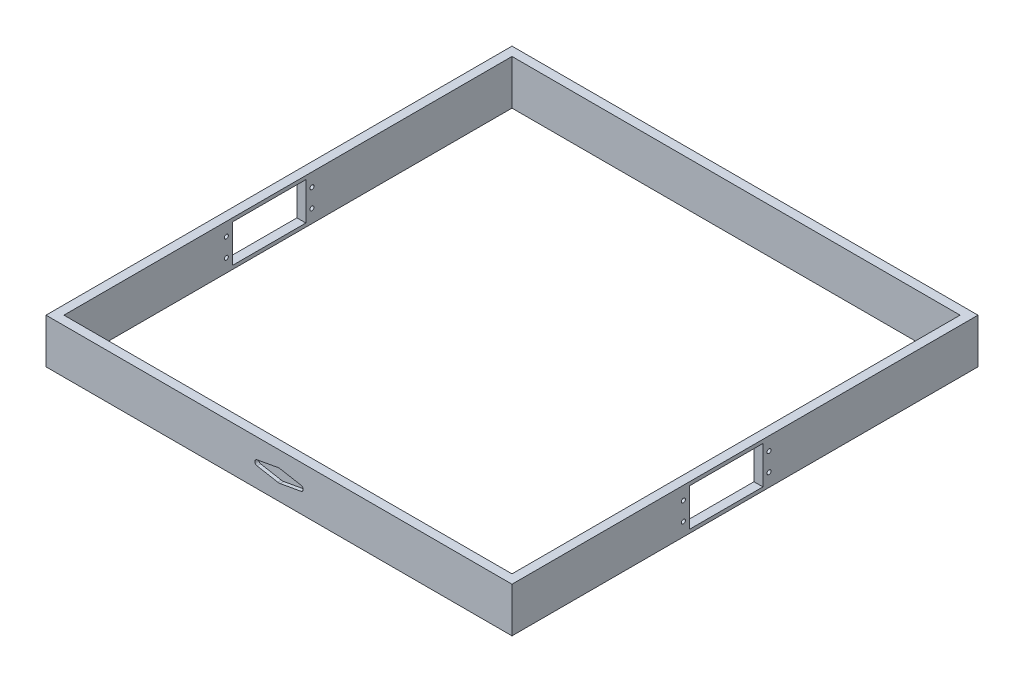
SolidWorks part; units mm, degrees
ref_plane "Front Plane" through (0, 0, 0) normal (0, 0, 1) x (1, 0, 0)
ref_plane "Top Plane" through (0, 0, 0) normal (0, 1, 0) x (1, 0, 0)
ref_plane "Right Plane" through (0, 0, 0) normal (1, 0, 0) x (0, 0, -1)
sketch "Sketch1" plane through (0, 0, 0) normal (0, 1, 0) x (1, 0, 0)
  line L1 (-130.1, -130.1) -> (130.1, -130.1)
  line L2 (-130.1, -130.1) -> (-130.1, 130.1)
  line L3 (-130.1, 130.1) -> (130.1, 130.1)
  line L4 (130.1, -130.1) -> (130.1, 130.1)
  line L5 (-130.1, -130.1) -> (130.1, 130.1) construction
  line L6 (-130.1, 130.1) -> (130.1, -130.1) construction
  point P0 (0, 0)
  dimension "D1" = 260.2
extrude "Boss-Extrude1" add sketch "Sketch1" along normal blind 25
sketch "Sketch2" plane through (0, 25, 0) normal (0, 1, 0) x (1, 0, 0)
  line L0 (130.1, 130.1) -> (-130.1, 130.1) construction
  line L1 (-125.1, -125.1) -> (125.1, -125.1)
  line L2 (-125.1, -125.1) -> (-125.1, 125.1)
  line L3 (-125.1, 125.1) -> (125.1, 125.1)
  line L4 (125.1, -125.1) -> (125.1, 125.1)
  line L5 (-125.1, -125.1) -> (125.1, 125.1) construction
  line L6 (-125.1, 125.1) -> (125.1, -125.1) construction
  point P0 (0, 0)
  dimension "D1" = 5
extrude "Cut-Extrude1" cut sketch "Sketch2" against normal blind 25
sketch "Sketch19" plane through (-130.1, 0, 0) normal (-1, 0, 0) x (0, 0, 1)
  line L0 (-130.1, 25) -> (-130.1, 0) construction
  line L1 (-10, 23) -> (31, 23)
  line L2 (-10, 23) -> (-10, 2)
  line L3 (-10, 2) -> (31, 2)
  line L4 (31, 23) -> (31, 2)
  line L5 (-10, 23) -> (31, 2) construction
  line L6 (-10, 2) -> (31, 23) construction
  line L7 (-130.1, 25) -> (130.1, 25) construction
  point P0 (10.5, 12.5)
  point P7 (-130.1, 12.5)
  point P10 (0, 25)
  dimension "D1" = 41
  dimension "D2" = 21
  dimension "D3" = 10
extrude "Cut-Extrude10" cut sketch "Sketch19" against normal through all
ref_plane "Plane5" through (0, 0, 10.5) normal (0, 0, 1) x (1, 0, 0)
ref_plane "Plane6" through (0, 12.5, 0) normal (0, 1, 0) x (1, 0, 0)
sketch "Sketch21" plane through (-130.1, 0, 0) normal (-1, 0, 0) x (0, 0, 1)
  line L2 (31, 23) -> (-10, 23) construction
  line L3 (-10, 23) -> (-10, 2) construction
  circle A0 centre (-13.4, 17.6) radius 1.125
  point P4 (-10, 12.5)
  point P9 (10.5, 23)
  dimension "D3" = 2.25
  dimension "D1" = 23.9
  dimension "D2" = 5.1
extrude "Cut-Extrude12" cut sketch "Sketch21" against normal through all
mirror "Mirror1" about plane through (0, 0, 10.5) normal (0, 0, 1) of "Cut-Extrude12" second plane through (0, 12.5, 0) second plane normal (0, 1, 0)
ref_plane "Plane7" through (0, 0, 0) normal (-1, 0, 0) x (0, 0, 1)
sketch "Sketch22" plane through (0, 0, 130.1) normal (0, 0, 1) x (1, 0, 0)
  line L0 (-130.1, 25) -> (-130.1, 0) construction
  line L1 (-12.2663, 13.9762) -> (-0.6443, 16.0724)
  line L2 (-12.2663, 11.0238) -> (-0.6443, 8.9276)
  line L3 (0.6443, 16.0724) -> (12.2662, 13.9762)
  line L4 (0.6443, 8.9276) -> (12.2662, 11.0238)
  line L5 (0, 16.13) -> (0, 8.87) construction
  arc A0 (-0.6443, 8.9276) -> (0.6443, 8.9276) centre (0, 12.5) ccw
  arc A1 (12.2662, 11.0238) -> (12.2662, 13.9762) centre (12, 12.5) ccw
  arc A2 (-12.2663, 13.9762) -> (-12.2663, 11.0238) centre (-12, 12.5) ccw
  arc A3 (0.6443, 16.0724) -> (-0.6443, 16.0724) centre (0, 12.5) ccw
  point P12 (-130.1, 12.5)
  point P22 (0, 10.0125)
  dimension "D1" = 7.26
  dimension "D4" = 3
  dimension "D3" = 12
extrude "Cut-Extrude13" cut sketch "Sketch22" against normal blind 2
mirror "Mirror2" about plane through (0, 0, 0) normal (0, 0, 1) of "Cut-Extrude13"
